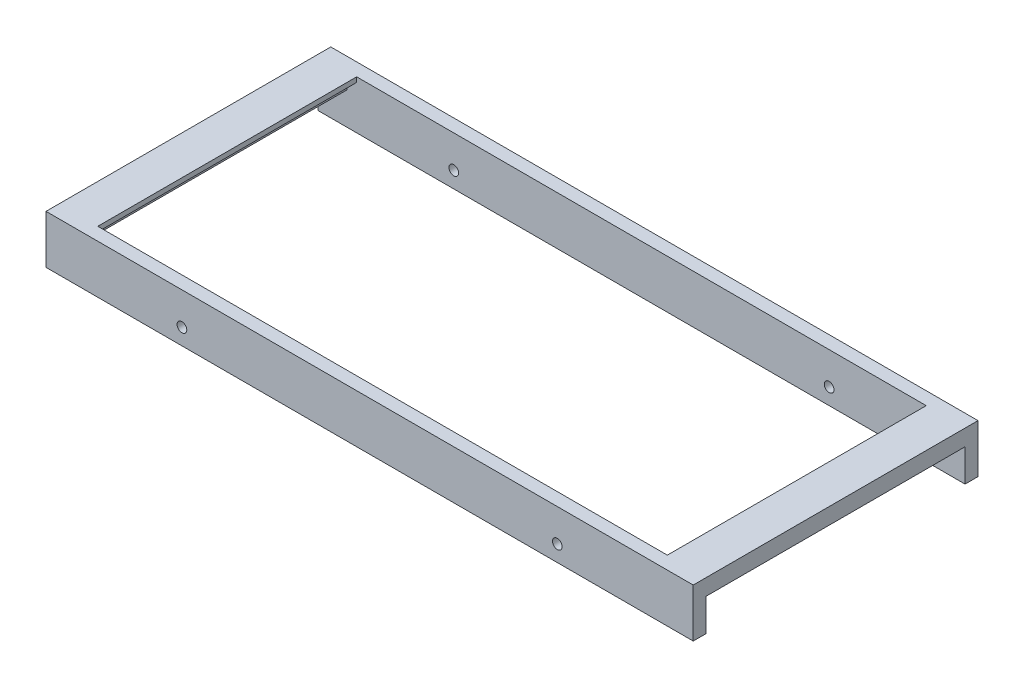
SolidWorks part; units mm, degrees
ref_plane "Front Plane" through (0, 0, 0) normal (0, 0, 1) x (1, 0, 0)
ref_plane "Top Plane" through (0, 0, 0) normal (0, 1, 0) x (1, 0, 0)
ref_plane "Right Plane" through (0, 0, 0) normal (1, 0, 0) x (0, 0, -1)
sketch "Sketch1" plane through (0, 0, 0) normal (0, 0, 1) x (1, 0, 0)
  line L0 (100, 33.5) -> (100, 0) construction
  line L1 (0, 0) -> (200, 0)
  line L2 (0, 0) -> (0, 33.5)
  line L3 (0, 33.5) -> (200, 33.5)
  line L4 (200, 0) -> (200, 33.5)
  line L5 (0, 28.5) -> (200, 28.5)
  line L6 (9, 28.5) -> (9, 33.5)
  line L7 (191, 28.5) -> (191, 33.5)
  circle A0 centre (158, 23.5) radius 1.5
  circle A3 centre (42, 23.5) radius 1.5
  dimension "D3" = 3
  dimension "D1" = 28.5
  dimension "D2" = 200
  dimension "D5" = 10
  dimension "D6" = 42
  dimension "D7" = 5
  dimension "D8" = 9
extrude "Mounting Plate" add sketch "Sketch1" along normal blind 4 contours L0 L3 L2 L5 | L3 L0 L5 L4 | L5 L6 L3 L2 | L7 L5 L4 L3 region at (149.9801, 14.227, 0) region at (50.0199, 14.227, 0) region at (4.5, 31, 0) region at (195.5, 31, 0)
sketch "Sketch3" plane through (0, 0, 0) normal (0, 0, -1) x (-1, 0, 0)
  line L0 (-100, 0) -> (-100, 41.373) construction
  line L1 (0, 33.5) -> (-9, 33.5)
  line L2 (0, 33.5) -> (0, 28.5)
  line L3 (0, 28.5) -> (-9, 28.5)
  line L4 (-9, 33.5) -> (-9, 28.5)
  line L5 (-9, 33.5) -> (-12, 33.5)
  line L6 (-9, 33.5) -> (-9, 32)
  line L7 (-9, 32) -> (-12, 32)
  line L8 (-12, 33.5) -> (-12, 32)
  line L9 (0, 0) -> (0, 33.5) construction
  line L10 (-188, 33.5) -> (-188, 32)
  line L11 (-191, 32) -> (-188, 32)
  line L12 (-191, 33.5) -> (-191, 32)
  line L13 (-191, 33.5) -> (-188, 33.5)
  line L14 (-191, 33.5) -> (-191, 28.5)
  line L15 (-200, 28.5) -> (-191, 28.5)
  line L16 (-200, 33.5) -> (-200, 28.5)
  line L17 (-200, 33.5) -> (-191, 33.5)
  line L18 (0, 0) -> (-200, 0) construction
  line L19 (0, 33.5) -> (-9, 33.5) construction
  line L20 (-9, 28.5) -> (-9, 33.5) construction
  dimension "D1" = 5
  dimension "D3" = 1.5
  dimension "D4" = 3
extrude "Rails" add sketch "Sketch3" along normal blind 80 contours L4 L3 | L7 L4 | L5 L8 L7 | L13 L11 L10 | L12 L11 | L15 L14 L12 region at (4.5, 31, 0) region at (10.5, 32.75, 0) region at (189.5, 32.75, 0) region at (195.5, 31, 0)
extrude "Mounting Plate 2" add sketch "Sketch1<4>" along normal blind 4 contours L0 L3 L6 L5 | L3 L0 L5 L7 region at (145.5, 31, 0) region at (54.5, 31, 0)
sketch "Sketch1<4>" plane through (0, 0, 0) normal (0, 0, 1) x (1, 0, 0) same geometry as "Sketch1"
ref_plane "Mirror Plane" through (0, 0, -40) normal (0, 0, 1) x (1, 0, 0)
mirror "Mirror1" about plane through (0, 0, -40) normal (0, 0, 1) of "Mounting Plate 2", "Mounting Plate"
sketch "Sketch4" plane through (0, 0, -84) normal (0, 0, -1) x (-1, 0, 0)
  line L0 (-200, 0) -> (-200, 33.5) construction
  line L1 (0, 33.5) -> (-200, 33.5)
  line L2 (0, 33.5) -> (0, 18.5)
  line L3 (0, 18.5) -> (-200, 18.5)
  line L4 (-200, 33.5) -> (-200, 18.5)
  line L5 (0, 0) -> (-200, 0) construction
  line L6 (0, 18.5) -> (-200, 18.5)
  line L7 (0, 18.5) -> (0, 0)
  line L8 (0, 0) -> (-200, 0)
  line L9 (-200, 18.5) -> (-200, 0)
  line M8 (-200, 33.5) -> (-200, 0)
  line M9 (-200, 0) -> (0, 0)
  line M10 (0, 0) -> (0, 33.5)
  dimension "D1" = 15
extrude "Unnecessary Plastic" cut sketch "Sketch4" against normal through all contours L3 M10 M8 M9 region at (100, 9.25, -84)
